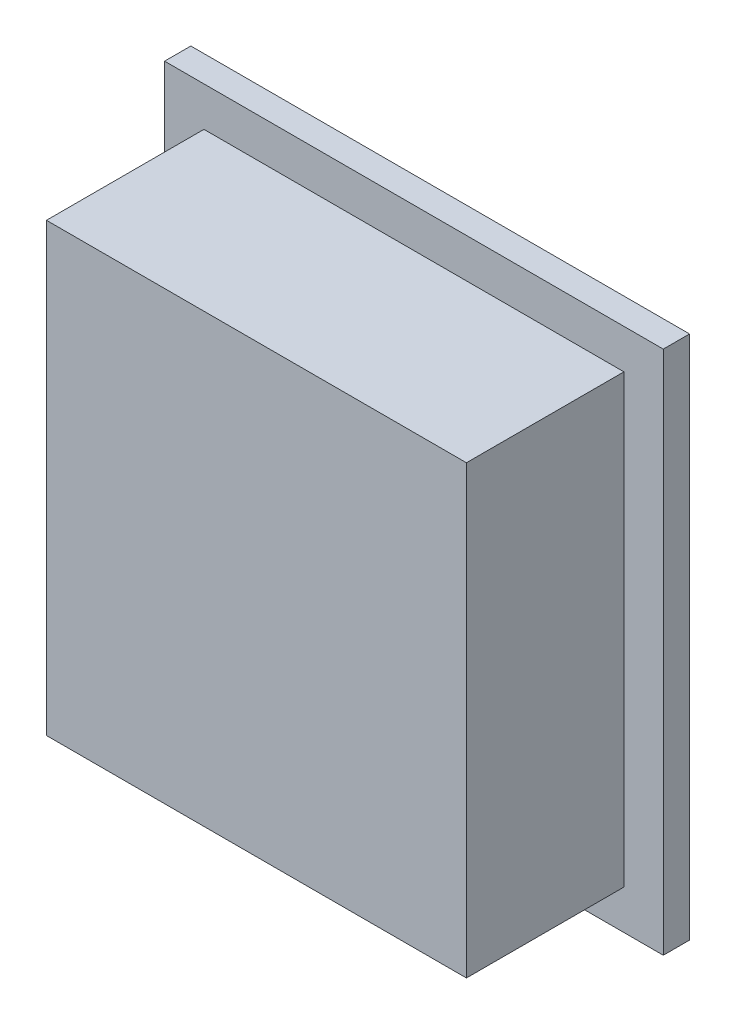
SolidWorks part; units mm, degrees
ref_plane "前视基准面" through (0, 0, 0) normal (0, 0, 1) x (1, 0, 0)
ref_plane "上视基准面" through (0, 0, 0) normal (0, 1, 0) x (1, 0, 0)
ref_plane "右视基准面" through (0, 0, 0) normal (1, 0, 0) x (0, 0, -1)
sketch "草图1" plane through (0, 0, 0) normal (0, 0, 1) x (1, 0, 0)
  line L1 (-80, -85) -> (80, -85)
  line L2 (-80, -85) -> (-80, 85)
  line L3 (-80, 85) -> (80, 85)
  line L4 (80, -85) -> (80, 85)
  line L5 (-80, -85) -> (80, 85) construction
  line L6 (-80, 85) -> (80, -85) construction
  point P0 (0, 0)
  dimension "D1" = 170
  dimension "D2" = 160
extrude "凸台-拉伸1" add sketch "草图1" along normal blind 60
sketch "草图2" plane through (0, 0, 0) normal (0, 0, -1) x (-1, 0, 0)
  line L1 (-95, -100) -> (95, -100)
  line L2 (-95, -100) -> (-95, 100)
  line L3 (-95, 100) -> (95, 100)
  line L4 (95, -100) -> (95, 100)
  line L5 (-95, -100) -> (95, 100) construction
  line L6 (-95, 100) -> (95, -100) construction
  point P0 (0, 0)
  dimension "D1" = 200
  dimension "D2" = 190
extrude "凸台-拉伸2" add sketch "草图2" along normal blind 10
